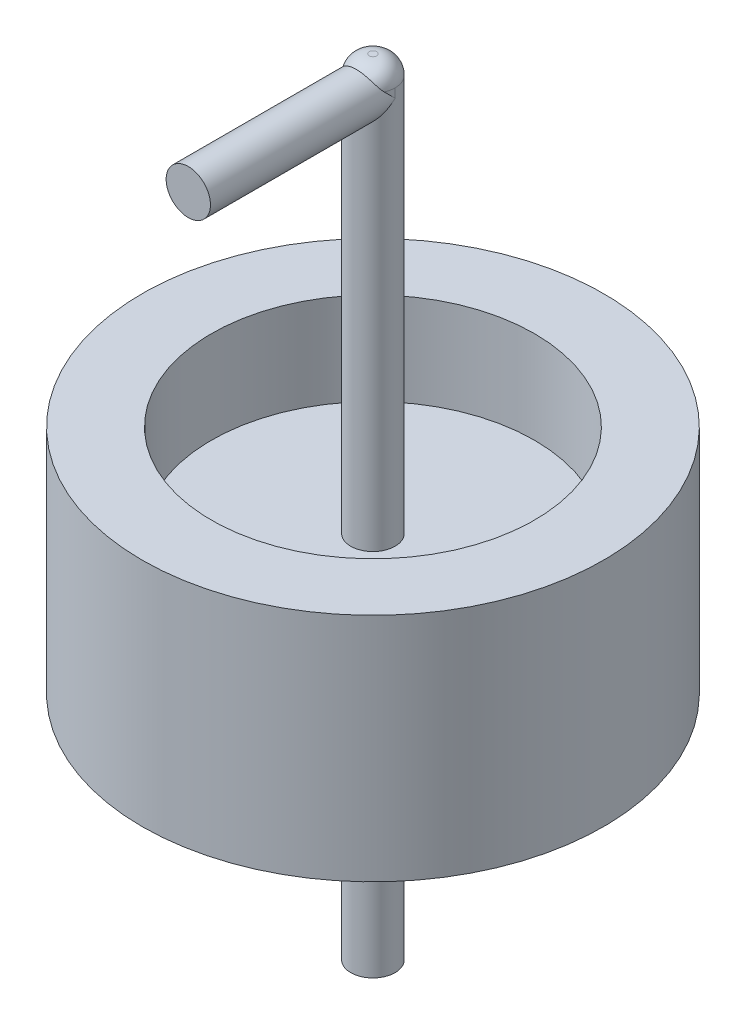
SolidWorks part; units mm, degrees
ref_plane "前视基准面" through (0, 0, 0) normal (0, 0, 1) x (1, 0, 0)
ref_plane "上视基准面" through (0, 0, 0) normal (0, 1, 0) x (1, 0, 0)
ref_plane "右视基准面" through (0, 0, 0) normal (1, 0, 0) x (0, 0, -1)
other "Configuration Table"
sketch "草图1" plane through (0, 0, 0) normal (0, 1, 0) x (1, 0, 0)
  circle A0 centre (0, 0) radius 25
  dimension "D1" = 50
extrude "凸台-拉伸1" add sketch "草图1" along normal blind 25
sketch "草图2" plane through (0, 0, 0) normal (0, -1, 0) x (1, 0, 0)
  circle A0 centre (0, 0) radius 17.5
  dimension "D1" = 35
extrude "切除-拉伸1" cut sketch "草图2" against normal blind 10
ref_plane "基准面1" through (0, 12.5, 0) normal (0, -1, 0) x (-1, 0, 0)
mirror "镜向1" about plane through (0, 12.5, 0) normal (0, -1, 0) of "切除-拉伸1"
sketch "草图3" plane through (0, 10, 0) normal (0, -1, 0) x (1, 0, 0)
  circle A0 centre (0, 0) radius 2.4
  dimension "D1" = 4.8
extrude "凸台-拉伸2" add sketch "草图3" along normal blind 35
extrude "凸台-拉伸3" add sketch "草图3<2>" against normal blind 50
sketch "草图3<2>" plane through (0, 10, 0) normal (0, -1, 0) x (1, 0, 0) same geometry as "草图3"
sketch "草图4" plane through (0, 0, 0) normal (0, 0, 1) x (1, 0, 0)
  circle A0 centre (0, 57.0287) radius 2.4
  dimension "D1" = 4.8
extrude "凸台-拉伸4" add sketch "草图4" along normal blind 20
fillet "圆角1" radius 2 1 edges at (0, 60, -2.4)
